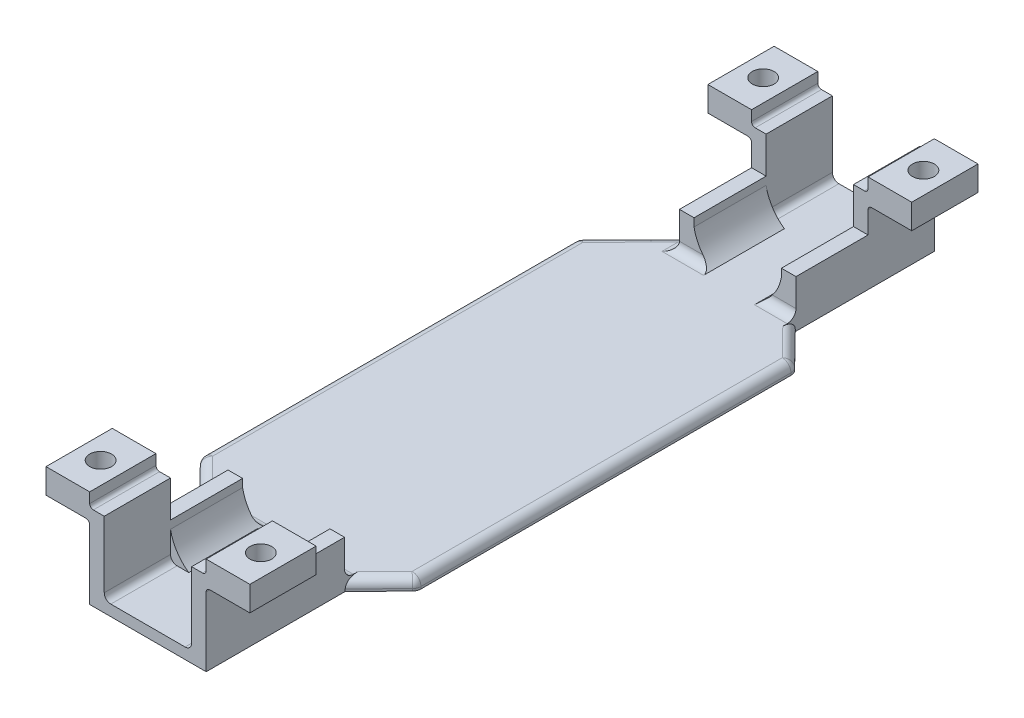
SolidWorks part; units mm, degrees
ref_plane "Front Plane" through (0, 0, 0) normal (0, 0, 1) x (1, 0, 0)
ref_plane "Top Plane" through (0, 0, 0) normal (0, 1, 0) x (1, 0, 0)
ref_plane "Right Plane" through (0, 0, 0) normal (1, 0, 0) x (0, 0, -1)
sketch "Sketch2" plane through (0, 0, 0) normal (0, 1, 0) x (1, 0, 0)
  line L1 (-8, -9.5) -> (8, -9.5)
  line L2 (-8, -9.5) -> (-8, 9.5)
  line L3 (-8, 9.5) -> (8, 9.5)
  line L4 (8, -9.5) -> (8, 9.5)
  line L5 (-8, -9.5) -> (8, 9.5) construction
  line L6 (-8, 9.5) -> (8, -9.5) construction
  point P0 (0, 0)
  dimension "D1" = 16
  dimension "D2" = 19
extrude "Boss-Extrude1" add sketch "Sketch2" along normal blind 13.3
sketch "Sketch3" plane through (0, 13.3, 0) normal (0, 1, 0) x (1, 0, 0)
  line L0 (8, 9.5) -> (-8, 9.5) construction
  line L1 (-6, -9.5) -> (6, -9.5)
  line L2 (-6, -9.5) -> (-6, 9.5)
  line L3 (-6, 9.5) -> (6, 9.5)
  line L4 (6, -9.5) -> (6, 9.5)
  line L5 (-6, -9.5) -> (6, 9.5) construction
  line L6 (-6, 9.5) -> (6, -9.5) construction
  point P0 (0, 0)
  dimension "D1" = 12
extrude "Cut-Extrude1" cut sketch "Sketch3" against normal blind 8.9
fillet "Fillet1" radius 2 2 edges at (-8, 13.3, 0) (8, 13.3, 0)
sketch "Sketch4" plane through (0, 0, 0) normal (1, 0, 0) x (0, 0, -1)
  line L0 (8.8, 0) -> (-8.8, 0) construction
  line L1 (-9.5, 13.3) -> (0.4, 13.3)
  line L2 (-9.5, 13.3) -> (-9.5, 9.4)
  line L3 (-9.5, 9.4) -> (0.4, 9.4)
  line L4 (0.4, 13.3) -> (0.4, 9.4)
  dimension "D1" = 9.9
  dimension "D2" = 9.4
extrude "Cut-Extrude2" cut sketch "Sketch4" against normal through all both and the other way through all
sketch "Sketch5" plane through (0, 0, 0) normal (1, 0, 0) x (0, 0, -1)
  line L0 (8.8, 0) -> (-8.8, 0) construction
  line L1 (-7, 2.7) -> (-3.2, 2.7)
  line L2 (-7, 2.7) -> (-7, 1)
  line L3 (-7, 1) -> (-3.2, 1)
  line L4 (-3.2, 2.7) -> (-3.2, 1)
  line L5 (-9.5, 9.4) -> (-9.5, 0) construction
  dimension "D1" = 3.8
  dimension "D2" = 1.7
  dimension "D3" = 1
  dimension "D4" = 2.5
extrude "Cut-Extrude3" cut sketch "Sketch5" against normal through all both and the other way through all
sketch "Sketch6" plane through (0, 0, 0) normal (0, 1, 0) x (1, 0, 0)
  line L0 (6, 9.5) -> (-6, 9.5) construction
  line L1 (-14, 9.5) -> (14, 9.5)
  line L2 (0, 9.5) -> (0, 0.4)
  line L3 (-14, 0.4) -> (14, 0.4)
  line L4 (14, 9.5) -> (14, 0.4)
  line L6 (0, -3.575) -> (0, 3.575) construction
  line L7 (-14, 9.5) -> (-14, 0.4)
  dimension "D1" = 9.1
  dimension "D2" = 14
extrude "Boss-Extrude2" add sketch "Sketch6" along normal blind 2.5 contours L4 L1 L2 L3 | L1 L7 L3 L2
sketch "Sketch7" plane through (0, 2.5, 0) normal (0, 1, 0) x (1, 0, 0)
  line L0 (-8, 9.5) -> (-8, 0.4) construction
  line L1 (-14, 9.5) -> (-8, 9.5) construction
  line L2 (0, -3.575) -> (0, 3.575) construction
  line L3 (-14, 9.5) -> (-14, 0.4) construction
  circle A0 centre (-11, 5) radius 1.55
  circle A1 centre (11, 5) radius 1.55
  dimension "D1" = 3.1
  dimension "D2" = 3
  dimension "D3" = 4.5
  dimension "D4" = 3
extrude "Cut-Extrude4" cut sketch "Sketch7" against normal through all both and the other way through all
sketch "Sketch14" plane through (0, 0, 0) normal (0, 0, 1) x (1, 0, 0)
  line L1 (-6, 13.3) -> (6, 13.3)
  line L2 (-6, 13.3) -> (-6, 4.4)
  line L3 (-6, 4.4) -> (6, 4.4)
  line L4 (6, 13.3) -> (6, 4.4)
extrude "Boss-Extrude3" add sketch "Sketch14" along normal blind 9.5
sketch "Sketch16" plane through (0, 0, 0) normal (0, 1, 0) x (1, 0, 0)
  line L1 (-14, 9.5) -> (14, 9.5)
  line L2 (-14, 9.5) -> (-14, 0.4)
  line L3 (-14, 0.4) -> (14, 0.4)
  line L4 (14, 9.5) -> (14, 0.4)
extrude "Cut-Extrude10" cut sketch "Sketch16" along normal through all both and the other way through all
sketch "Sketch17" plane through (0, 0, 0) normal (0, 1, 0) x (1, 0, 0)
  line L1 (-8, -9.5) -> (8, -9.5)
  line L2 (-8, -9.5) -> (-8, -71.5)
  line L3 (-8, -71.5) -> (8, -71.5)
  line L4 (8, -9.5) -> (8, -71.5)
  dimension "D1" = 62
  dimension "D2" = 16
extrude "Boss-Extrude5" add sketch "Sketch17" along normal blind 4.4
sketch "Sketch22" plane through (0, 0, 0) normal (0, 1, 0) x (1, 0, 0)
  line L0 (-3.575, 0) -> (3.575, 0) construction
  line L1 (-6, 0.4) -> (6.0328, 0.4)
  line L2 (-6, 0.4) -> (-6, 0)
  line L3 (-6, 0) -> (6.0328, 0)
  line L4 (6.0328, 0.4) -> (6.0328, 0)
extrude "Boss-Extrude7" add sketch "Sketch22" along normal blind 9.4
sketch "Sketch20" plane through (0, 0, 0) normal (0, 1, 0) x (1, 0, 0)
  line L1 (-8, -71.5) -> (8, -71.5)
  line L2 (-8, -71.5) -> (-8, -81.4)
  line L3 (-8, -81.4) -> (8, -81.4)
  line L4 (8, -71.5) -> (8, -81.4)
  dimension "D1" = 9.9
  dimension "D2" = 16
extrude "Boss-Extrude6" add sketch "Sketch20" along normal blind 9.4
sketch "Sketch24" plane through (0, 0, 0) normal (0, 1, 0) x (1, 0, 0)
  line L1 (-8, -81.4) -> (8, -81.4)
  line L2 (-8, -81.4) -> (-8, -90.5)
  line L3 (-8, -90.5) -> (8, -90.5)
  line L4 (8, -81.4) -> (8, -90.5)
  line L5 (8, 0.4) -> (-8, 0.4)
  line L6 (8, 0.4) -> (8, 9.5)
  line L7 (8, 9.5) -> (-8, 9.5)
  line L8 (-8, 0.4) -> (-8, 9.5)
  dimension "D1" = 9.1
  dimension "D2" = 16
  dimension "D3" = 9.1
  dimension "D4" = 16
extrude "Boss-Extrude8" add sketch "Sketch24" along normal blind 4.4
sketch "Sketch21" plane through (0, 0, 0) normal (1, 0, 0) x (0, 0, -1)
  line L0 (8.8, 0) -> (-8.8, 0) construction
  line L1 (-81.4, 0) -> (918.6, 0)
  line L2 (-81.4, 0) -> (-81.4, 2.9)
  line L3 (-81.4, 2.9) -> (918.6, 2.9)
  line L4 (918.6, 0) -> (918.6, 2.9)
  line L5 (-81.4, 9.4) -> (-81.4, 4.4) construction
  line L6 (-71.5, 4.4) -> (-9.5, 4.4) construction
  dimension "D1" = 1.5
  dimension "D2" = 1000
extrude "Cut-Extrude11" cut sketch "Sketch21" against normal through all both and the other way through all
sketch "Sketch15" plane through (0, 0, 0) normal (0, 0, 1) x (1, 0, 0)
  line L0 (0, -3.575) -> (0, 3.575) construction
  line L1 (-6, 4.4) -> (6, 4.4) construction
  line L2 (-6, 4.4) -> (6, 4.4)
  line L7 (-6, 13.3) -> (6, 13.3)
  line L8 (-6, 13.3) -> (-6, 9.4)
  line L9 (-6, 9.4) -> (6, 9.4)
  line L10 (6, 13.3) -> (6, 9.4)
  line L11 (6, 13.3) -> (6, 4.4)
  line L12 (6, 13.3) -> (6, 4.4)
  line L13 (-6, 13.3) -> (-6, 4.4)
  circle A0 centre (0, 9.4) radius 6.1
  dimension "D1" = 12.2
  dimension "D2" = 5
extrude "Cut-Extrude9" cut sketch "Sketch15" against normal blind 1000 and the other way blind 81.4 contours L7 A0 | L9 A0 L7 | L9 A0 L2 | A0 L7 L8
sketch "Sketch25" plane through (0, 4.4, 0) normal (0, 1, 0) x (1, 0, 0)
  line L0 (6, 0.4) -> (8, 0.4) construction
  line L1 (8, -90.5) -> (6, -90.5)
  line L2 (8, -90.5) -> (8, -81.4)
  line L3 (8, -81.4) -> (6, -81.4)
  line L4 (6, -90.5) -> (6, -81.4)
  line L5 (-8, -90.5) -> (-6, -90.5)
  line L6 (-8, -90.5) -> (-8, -81.4)
  line L7 (-8, -81.4) -> (-6, -81.4)
  line L8 (-6, -90.5) -> (-6, -81.4)
  line L9 (-8, 9.5) -> (-6, 9.5)
  line L10 (-8, 9.5) -> (-8, 0.4)
  line L11 (-8, 0.4) -> (-6, 0.4)
  line L12 (-6, 9.5) -> (-6, 0.4)
  line L13 (8, 9.5) -> (6, 9.5)
  line L14 (8, 9.5) -> (8, 0.4)
  line L15 (8, 0.4) -> (6, 0.4)
  line L16 (6, 9.5) -> (6, 0.4)
  line L17 (3.4943, 0.4) -> (8, 0.4) construction
extrude "Boss-Extrude9" add sketch "Sketch25" along normal blind 10
fillet "Fillet4" radius 0.9 4 edges at (6, 4.4, 85.95) (-6, 4.4, 85.95) (-6, 4.4, -4.95) (6, 4.4, -4.95)
sketch "Sketch26" plane through (8, 0, 0) normal (1, 0, 0) x (0, 0, -1)
  line L0 (9.5, 2.9) -> (-81.4, 2.9) construction
  line L1 (-91.3554, -1.7985) -> (-79.9561, -1.7985)
  line L2 (-91.3554, -1.7985) -> (-91.3554, 2.9)
  line L3 (-91.3554, 2.9) -> (-79.9561, 2.9)
  line L4 (-79.9561, -1.7985) -> (-79.9561, 2.9)
extrude "Cut-Extrude12" cut sketch "Sketch26" against normal through all both and the other way through all
sketch "Sketch27" plane through (0, 14.4, 0) normal (0, 1, 0) x (1, 0, 0)
  line L0 (-14, -40.5) -> (16.7963, -40.5)
  line L1 (8, 9.5) -> (14, 9.5)
  line L2 (8, 9.5) -> (8, 0.4)
  line L3 (8, 0.4) -> (14, 0.4)
  line L4 (14, 9.5) -> (14, 0.4)
  line L5 (-8, 9.5) -> (-14, 9.5)
  line L6 (-8, 9.5) -> (-8, 0.4)
  line L7 (-8, 0.4) -> (-14, 0.4)
  line L8 (-14, 9.5) -> (-14, 0.4)
  line L9 (8, -9.5) -> (3.4943, -9.5) construction
  line L10 (0, -7.315) -> (0, 7.315) construction
  line L11 (8, -81.4) -> (14, -81.4)
  line L12 (14, -90.5) -> (14, -81.4)
  line L13 (8, -90.5) -> (14, -90.5)
  line L14 (8, -90.5) -> (8, -81.4)
  line L15 (-8, -81.4) -> (-14, -81.4)
  line L16 (-14, -90.5) -> (-14, -81.4)
  line L17 (-8, -90.5) -> (-14, -90.5)
  line L18 (-8, -90.5) -> (-8, -81.4)
  circle A0 centre (-11, 5) radius 1.5
  circle A1 centre (11, 5) radius 1.5
  circle A2 centre (11, -86) radius 1.5
  circle A3 centre (-11, -86) radius 1.5
  point P16 (0, 0)
  point P18 (-10.6998, 5.4738)
  point P19 (-14, 4.3083)
  line M16 (8, 0.4) -> (8, 9.5)
  dimension "D6" = 3
  dimension "D1" = 9.1
  dimension "D2" = 9.1
  dimension "D3" = 6
  dimension "D4" = 6
  dimension "D5" = 31
  dimension "D7" = 3
  dimension "D8" = 4.5
extrude "Boss-Extrude10" add sketch "Sketch27" along normal blind 1.9 and the other way blind 1.5 contours L14 L13 L12 L11 A2 | L17 L18 L15 L16 A3 | L5 L8 L7 L6 A0 | L4 L1 L3 A1 M16
fillet "Fillet10" radius 0.5 4 edges at (8, 12.9, 85.95) (-8, 12.9, -4.95) (8, 12.9, -4.95) (-8, 12.9, 85.95)
fillet "Fillet11" radius 0.5 4 edges at (8, 14.4, 85.95) (-8, 14.4, 85.95) (-8, 14.4, -4.95) (8, 14.4, -4.95)
sketch "Sketch28" plane through (0, 2.9, 0) normal (0, -1, 0) x (1, 0, 0)
  line L0 (-7.9051, 71.5) -> (-7.9051, 9.5) construction
  line L1 (-12.9051, 66.4) -> (12.9051, 66.4)
  line L2 (-12.9051, 66.4) -> (-12.9051, 14.6)
  line L3 (-12.9051, 14.6) -> (12.9051, 14.6)
  line L4 (0, 66.4) -> (0, 14.6)
  line L6 (0, -7.37) -> (0, 7.37) construction
  line L7 (-8.5, 81.4) -> (-14, 81.4) construction
  line L11 (-12.9051, 66.4) -> (-7.9051, 71.5)
  line L12 (-7.9051, 71.5) -> (7.9051, 71.5)
  line L13 (0, 71.5) -> (0, 66.4)
  line L14 (-12.9051, 14.6) -> (-7.9051, 9.5)
  line L15 (-7.9051, 9.5) -> (7.9051, 9.5)
  line L16 (0, 9.5) -> (0, 14.6)
  line L17 (12.9051, 66.4) -> (7.9051, 71.5)
  line L18 (12.9051, 14.6) -> (7.9051, 9.5)
  line L19 (12.9051, 66.4) -> (12.9051, 14.6)
  line L20 (-16.9051, 14.6) -> (-11.9051, 9.5)
  line L21 (-12.9051, 66.4) -> (-16.9051, 66.4)
  line L22 (-12.9051, 66.4) -> (-12.9051, 14.6)
  line L23 (-12.9051, 14.6) -> (-16.9051, 14.6)
  line L24 (-16.9051, 66.4) -> (-16.9051, 14.6)
  line L25 (-11.9051, 9.5) -> (-8, 5.5949)
  line L26 (-7.9051, 71.5) -> (-11.9051, 71.5)
  line L27 (-16.9051, 66.4) -> (-11.9051, 71.5)
  line L28 (-7.9051, 9.5) -> (-11.9051, 9.5)
  line L29 (-11.9051, 9.5) -> (-16.9051, 14.6)
  line L30 (-8, -9.5) -> (-8, 90.5) construction
  line L31 (-11.9051, 71.5) -> (-8, 75.4051)
  dimension "D1" = 5
  dimension "D2" = 0
  dimension "D3" = 15
  dimension "D4" = 15
  dimension "D5" = 4
  dimension "D6" = 0
  dimension "D7" = 4
extrude "Boss-Extrude11" add sketch "Sketch28" against normal blind 1.5
fillet "Fillet16" radius 1.2 18 edges at (12.9051, 3.65, 14.6) (12.9051, 3.65, 66.4) (-16.9051, 3.65, 14.6) (-16.9051, 3.65, 66.4) (10.4526, 4.4, 68.9016) (12.9051, 4.4, 40.5) (10.4526, 4.4, 12.0984) (-14.4051, 4.4, 12.05) (-16.9051, 4.4, 40.5) (-14.4051, 4.4, 68.95) (-8, 4.4, 7.5474) (-8, 4.4, 73.4526) (-9.9526, 4.4, 7.5474) (-9.9526, 4.4, 73.4526) (-8, 3.65, 5.5949) (-8, 3.65, 75.4051) (-11.9051, 3.65, 71.5) (-11.9051, 3.65, 9.5)
fillet "Fillet17" radius 1.2 4 edges at (-6.3471, 4.4, 9.5) (5.7471, 4.4, 9.5) (5.7471, 4.4, 71.5) (-6.3471, 4.4, 71.5)
